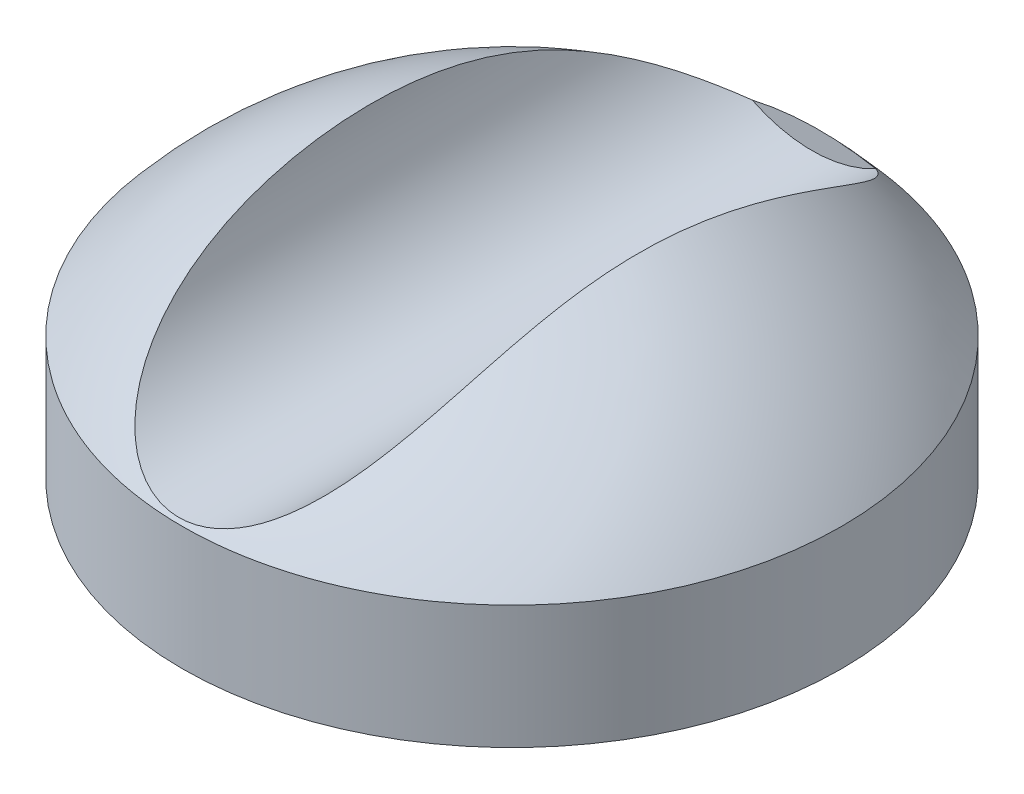
SolidWorks part; units mm, degrees
ref_plane "Front Plane" through (0, 0, 0) normal (0, 0, 1) x (1, 0, 0)
ref_plane "Top Plane" through (0, 0, 0) normal (0, 1, 0) x (1, 0, 0)
ref_plane "Right Plane" through (0, 0, 0) normal (1, 0, 0) x (0, 0, -1)
sketch "Sketch1" plane through (0, 0, 0) normal (0, 1, 0) x (1, 0, 0)
  circle A0 centre (0, 0) radius 106.9267
extrude "Boss-Extrude1" add sketch "Sketch1" along normal blind 40
dome "Dome1" faces to dome 1 distance 50 reverse direction no elliptical dome no face at (0, 40, 106.9267) parameters "D1"=50
sketch "Sketch2" plane through (0, 0, 0) normal (0, -1, 0) x (-1, 0, 0)
  line L17 (-5.9135, 99.6702) -> (-0.3403, 99.6702)
  line L18 (-5.9135, 99.6702) -> (-5.9135, 89.5491)
  line L19 (-5.9135, 89.5491) -> (-0.3403, 89.5491)
  line L20 (-0.3403, 99.6702) -> (-0.3403, 89.5491)
extrude "Boss-Extrude3" add sketch "Sketch2" along normal blind 0.1
sketch "Sketch3" plane through (0, 0, -99.6702) normal (0, 0, -1) x (-1, 0, 0)
  circle A0 centre (2.4316, 84.5377) radius 43.5
  point P2 (0, -5.5334)
  point P3 (0, -5.9781)
  point P4 (2.4316, 84.5377)
  dimension "D1" = 87
extrude "Cut-Extrude2" cut sketch "Sketch3" against normal through all
